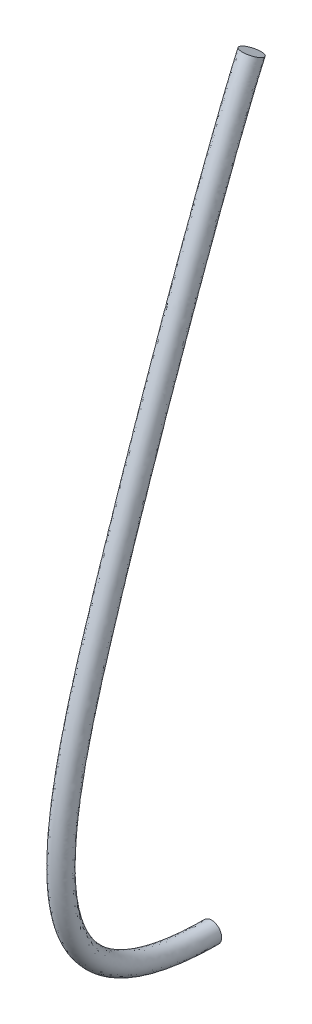
SolidWorks part; units mm, degrees
material "PVC 0.007 Plasticized"
ref_plane "Front Plane" through (0, 0, 0) normal (0, 0, 1) x (1, 0, 0)
ref_plane "Top Plane" through (0, 0, 0) normal (0, 1, 0) x (1, 0, 0)
ref_plane "Right Plane" through (0, 0, 0) normal (1, 0, 0) x (0, 0, -1)
sketch3d "3DSketch1"
  circle A0 centre (72.5, 25.85, 22.25) radius 3.5 construction
  circle A1 centre (72.5, 25.85, 22.25) radius 3.5 construction
  point P2 (72.5, 25.85, 25.75)
  point P4 (72.5, 25.85, 25.75)
  point P5 (72.5, 25.85, 22.25)
ref_plane "Plane1" through (72.5, 0, 0) normal (-1, 0, 0) x (0, 0, 1)
sketch "Sketch2" plane through (72.5, 0, 0) normal (-1, 0, 0) x (0, 0, 1)
  spline S0 degree 3 poles (22.25, 25.85) (62.7241, 26.0501) (45.4218, 92.0798) (18.6268, 163.5987) (14.3006, 172.916) knots 0 0 0 0 0.510096 1 1 1 1
  point P3 (46.3351, 33.8727)
  point P5 (14.3006, 172.916)
sweep "Sweep2" add path "Sketch2" circular profile diameter 4 parameters "D3"=4
